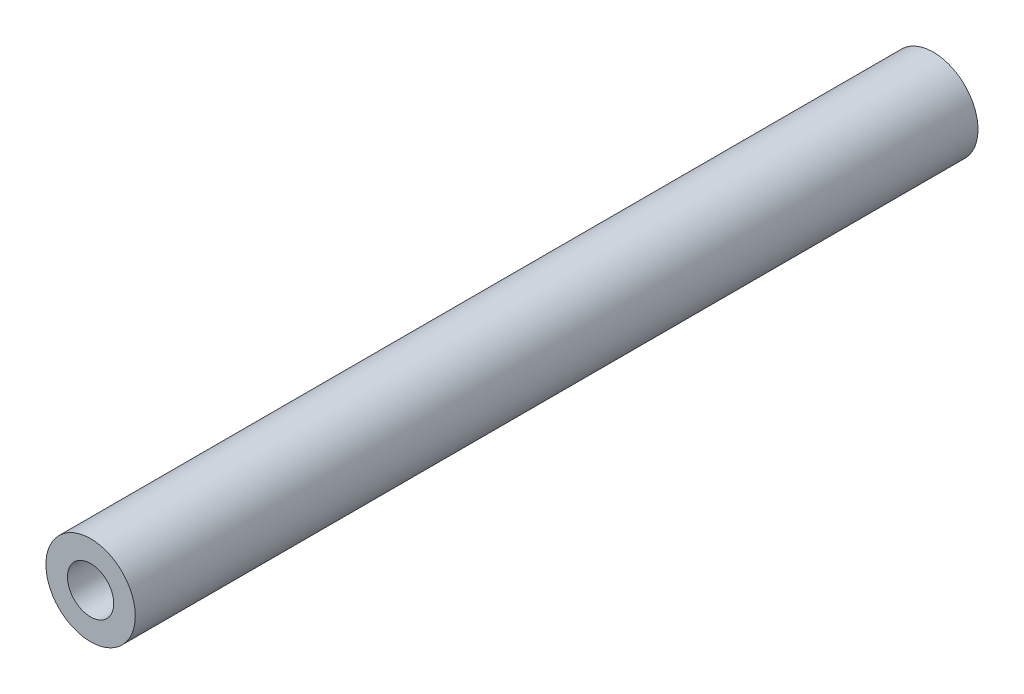
SolidWorks part; units mm, degrees
material "6061 Alloy"
ref_plane "Front Plane" through (0, 0, 0) normal (0, 0, 1) x (1, 0, 0)
ref_plane "Top Plane" through (0, 0, 0) normal (0, 1, 0) x (1, 0, 0)
ref_plane "Right Plane" through (0, 0, 0) normal (1, 0, 0) x (0, 0, -1)
sketch "Sketch1" plane through (0, 0, 0) normal (0, 0, 1) x (1, 0, 0)
  circle A0 centre (0, 0) radius 5
  dimension "D1" = 10
extrude "Boss-Extrude1" add sketch "Sketch1" along normal blind 94.3
hole_wizard "#6 (0.204) Diameter Hole1" positions "Sketch2" profile "Sketch3" hole size "#6" standard "ANSI Inch"
sketch "Sketch2" plane through (0, 0, 0) normal (0, 0, -1) x (-1, 0, 0)
  point P0 (0, 0)
sketch "Sketch3" plane through (0, 0, 0) normal (1, 0, 0) x (0, 1, 0)
  line L0 (0, 0) -> (0, 31.5567)
  line L1 (0, 31.5567) -> (2.5908, 30)
  line L2 (2.5908, 30) -> (2.5908, 0)
  line L5 (2.5908, 0) -> (0, 0)
  line L10 (0, 31.5567) -> (-2.5908, 30) construction
  line L11 (0, -6.35) -> (0, 107.95) construction
  dimension "Hole Dia." = 5.1816
  dimension "Hole Depth" = 30
  dimension "Drill Angle" = 118
hole_wizard "#6 (0.204) Diameter Hole2" positions "Sketch4" profile "Sketch5" hole size "#6" standard "ANSI Inch"
sketch "Sketch4" plane through (0, 0, 94.3) normal (0, 0, 1) x (1, 0, 0)
  point P0 (0, 0)
sketch "Sketch5" plane through (0, 0, 94.3) normal (1, 0, 0) x (0, -1, 0)
  line L0 (0, 0) -> (0, 31.5567)
  line L1 (0, 31.5567) -> (2.5908, 30)
  line L2 (2.5908, 30) -> (2.5908, 0)
  line L5 (2.5908, 0) -> (0, 0)
  line L10 (0, 31.5567) -> (-2.5908, 30) construction
  line L11 (0, -6.35) -> (0, 107.95) construction
  dimension "Hole Dia." = 5.1816
  dimension "Hole Depth" = 30
  dimension "Drill Angle" = 118
